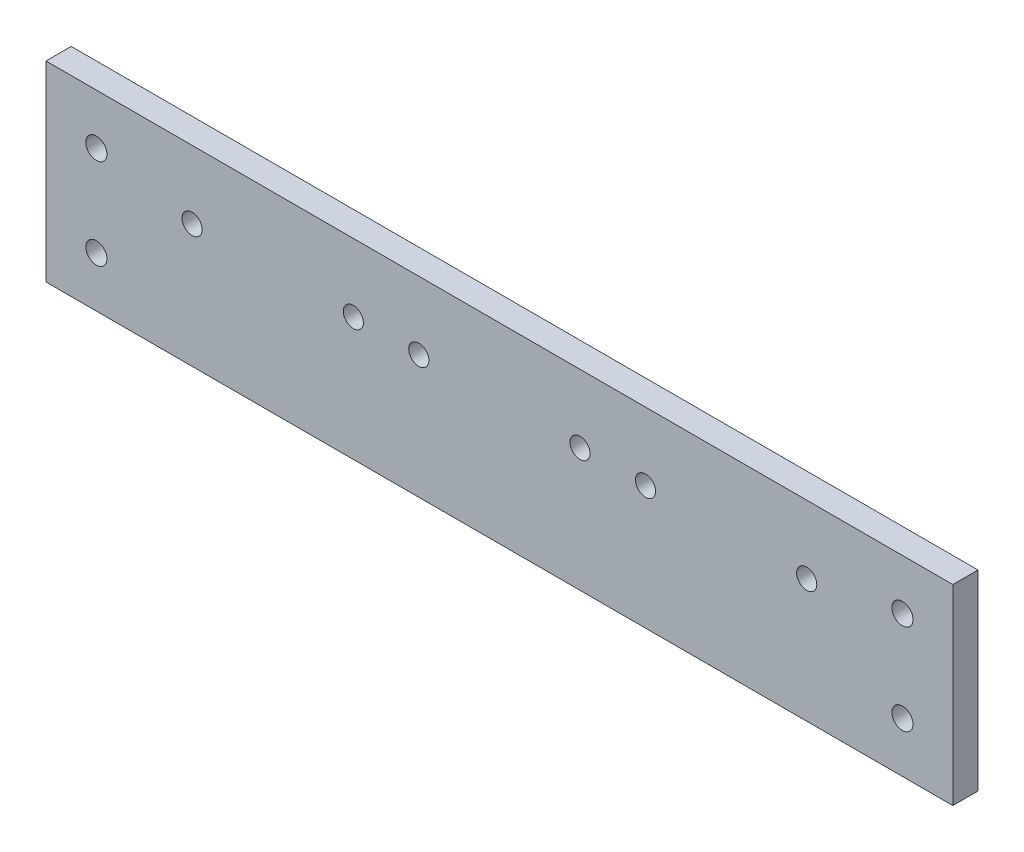
SolidWorks part; units mm, degrees
material "ABS"
ref_plane "Front Plane" through (0, 0, 0) normal (0, 0, 1) x (1, 0, 0)
ref_plane "Top Plane" through (0, 0, 0) normal (0, 1, 0) x (1, 0, 0)
ref_plane "Right Plane" through (0, 0, 0) normal (1, 0, 0) x (0, 0, -1)
sketch "Sketch1" plane through (0, 0, 0) normal (0, 0, 1) x (1, 0, 0)
  line L1 (0, -38) -> (180, -38)
  line L2 (0, -38) -> (0, 0)
  line L3 (0, 0) -> (180, 0)
  line L4 (180, -38) -> (180, 0)
  circle A0 centre (170, -10) radius 2.1
  circle A1 centre (170, -27.9969) radius 2.1
  circle A2 centre (10, -10) radius 2.1
  circle A3 centre (10, -27.9969) radius 2.1
  dimension "D3" = 10
  dimension "D6" = 4.2
  dimension "D1" = 180
  dimension "D2" = 38
  dimension "D4" = 10
  dimension "D5" = 10
  dimension "D7" = 17.9969
extrude "Boss-Extrude1" add sketch "Sketch1" along normal blind 5
sketch "Sketch3" plane through (0, 0, 5) normal (0, 0, 1) x (1, 0, 0)
  line L0 (180, 0) -> (0, 0) construction
  line L1 (180, -38) -> (180, 0) construction
  circle A0 centre (151, -13.5) radius 2
  circle A1 centre (119, -13.5) radius 2
  circle A2 centre (106, -13.5) radius 2
  circle A3 centre (74, -13.5) radius 2
  circle A4 centre (61, -13.5) radius 2
  circle A5 centre (29, -13.5) radius 2
  dimension "D1" = 4
  dimension "D4" = 29
  dimension "D5" = 32
  dimension "D2" = 13.5
  dimension "D3" = 32
  dimension "D6" = 32
  dimension "D7" = 13
  dimension "D8" = 13
extrude "Cut-Extrude2" cut sketch "Sketch3" against normal blind 22
